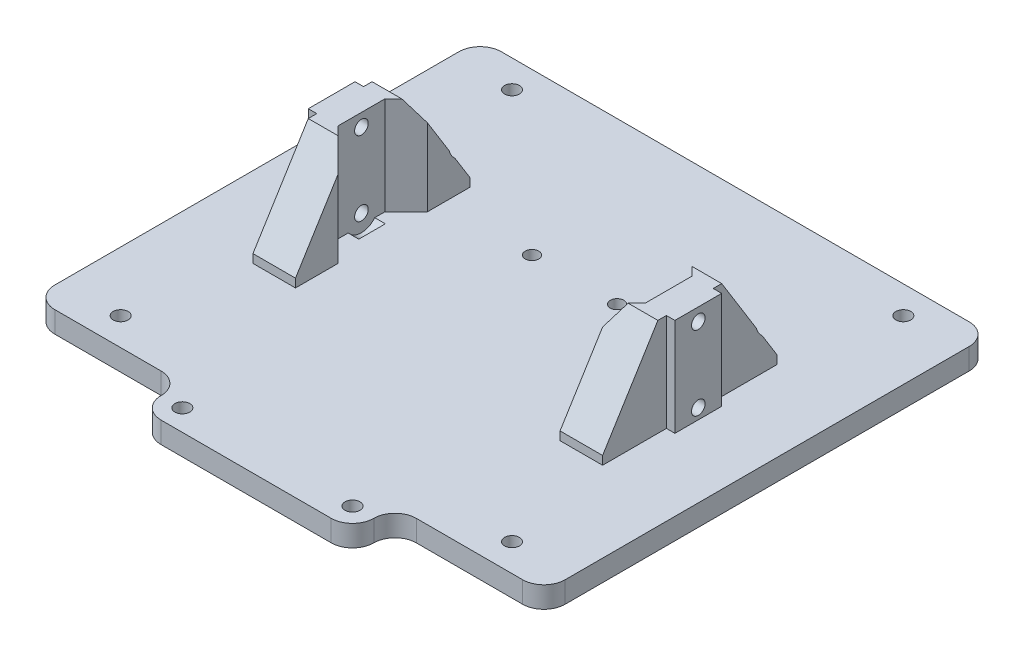
SolidWorks part; units mm, degrees
ref_plane "정면" through (0, 0, 0) normal (0, 0, 1) x (1, 0, 0)
ref_plane "윗면" through (0, 0, 0) normal (0, 1, 0) x (1, 0, 0)
ref_plane "우측면" through (0, 0, 0) normal (1, 0, 0) x (0, 0, -1)
sketch "스케치1" plane through (0, 0, 0) normal (0, 1, 0) x (1, 0, 0)
  line L0 (-25, -52.5) -> (-60, -52.5)
  line L1 (60, 52.5) -> (-60, 52.5)
  line L2 (60, 52.5) -> (60, -52.5)
  line L3 (60, -52.5) -> (25, -52.5)
  line L4 (-60, 52.5) -> (-60, -52.5)
  line L5 (60, 52.5) -> (-60, -52.5) construction
  line L6 (60, -52.5) -> (-60, 52.5) construction
  line L7 (25, -62.5) -> (-25, -62.5)
  line L8 (25, -62.5) -> (25, -52.5)
  line L10 (-25, -62.5) -> (-25, -52.5)
  line L11 (25, -62.5) -> (-25, -52.5) construction
  line L12 (25, -52.5) -> (-25, -62.5) construction
  point P0 (0, 0)
  point P6 (0, -57.5)
  dimension "D1" = 120
  dimension "D2" = 105
  dimension "D3" = 50
  dimension "D4" = 10
extrude "보스-돌출1" add sketch "스케치1" along normal blind 5
fillet "필렛1" radius 5 8 edges at (60, 2.5, -52.5) (60, 2.5, 52.5) (-60, 2.5, -52.5) (-60, 2.5, 52.5) (-25, 2.5, 52.5) (25, 2.5, 52.5) (25, 2.5, 62.5) (-25, 2.5, 62.5)
sketch "스케치2" plane through (0, 5, 0) normal (0, 1, 0) x (1, 0, 0)
  line L0 (-43.1, 29.5) -> (-43.1, -5.3) construction
  line L1 (-36.1, -4.8) -> (-43.1, -4.8)
  line L2 (-36.1, -4.8) -> (-36.1, 6.2)
  line L3 (-36.1, 6.2) -> (-43.1, 6.2)
  line L4 (-43.1, -4.8) -> (-43.1, 6.2)
  line L5 (-61.9, -0.8) -> (-43.1, -0.8) construction
  line L6 (-43.1, 2.2) -> (-61.9, 2.2) construction
  dimension "D1" = 7
  dimension "D2" = 4
  dimension "D3" = 4
extrude "보스-돌출2" add sketch "스케치2" along normal blind 23 separate body
sketch "스케치3" plane through (-36.1, 0, 0) normal (1, 0, 0) x (0, 0, -1)
  circle A0 centre (0.7, 7.5) radius 1.5 construction
  circle A1 centre (0.7, 25) radius 1.5 construction
  circle A2 centre (0.7, 25) radius 1.6
  circle A3 centre (0.7, 7.5) radius 1.6
  circle A4 centre (0.7, 7.5) radius 1.5 construction
  circle A5 centre (0.7, 25) radius 1.5 construction
  dimension "D1" = 3.2
  dimension "D2" = 3.2
extrude "컷-돌출1" cut sketch "스케치3" against normal through all
mirror "대칭 복사1" about plane through (0, 0, 0) normal (1, 0, 0) of bodies 103
sketch "스케치5" plane through (0, 5, 0) normal (0, 1, 0) x (1, 0, 0)
  circle A0 centre (-46, -46) radius 1.75 construction
  circle A1 centre (-46, 46) radius 1.75 construction
  circle A2 centre (46, 46) radius 1.75 construction
  circle A3 centre (46, -46) radius 1.75 construction
  circle A4 centre (-46, -46) radius 1.75
  circle A5 centre (-46, 46) radius 1.75
  circle A6 centre (46, 46) radius 1.75
  circle A7 centre (46, -46) radius 1.75
extrude "컷-돌출3" cut sketch "스케치5" against normal through all
sketch "스케치6" plane through (0, 5, 0) normal (0, 1, 0) x (1, 0, 0)
  circle A0 centre (20, -57.5) radius 1.75 construction
  circle A1 centre (-20, -57.5) radius 1.75 construction
  circle A2 centre (20, -57.5) radius 1.75
  circle A3 centre (-20, -57.5) radius 1.75
extrude "컷-돌출4" cut sketch "스케치6" against normal through all
sketch "Sketch2" plane through (36.1, 0, 0) normal (-1, 0, 0) x (0, 0, 1)
  circle A0 centre (-0.7, 7.5) radius 4
  dimension "D1" = 8
extrude "Cut-Extrude1" cut sketch "Sketch2" along normal blind 2.5
sketch "Sketch3" plane through (-36.1, 0, 0) normal (1, 0, 0) x (0, 0, -1)
  circle A0 centre (0.7, 7.5) radius 4
  dimension "D1" = 8
extrude "Cut-Extrude2" cut sketch "Sketch3" along normal blind 2.5
sketch "Sketch4" plane through (0, 5, 0) normal (0, 1, 0) x (1, 0, 0)
  line L0 (-10, 0) -> (10, 0) construction
  line L1 (10, 0) -> (10, 14.7) construction
  line L2 (10, 14.7) -> (-10, 14.7) construction
  line L3 (-10, 14.7) -> (-10, 0) construction
  line L4 (55, 52.5) -> (-55, 52.5) construction
  circle A0 centre (10, 0) radius 1.5 construction
  circle A1 centre (-10, 0) radius 1.5 construction
  circle A2 centre (10, 0) radius 1.5 construction
  circle A3 centre (-10, 0) radius 1.5 construction
  circle A4 centre (-10, 0) radius 1.6
  circle A5 centre (10, 0) radius 1.6
  circle A6 centre (-10, 14.7) radius 1.6
  circle A7 centre (10, 14.7) radius 1.6
  dimension "D1" = 3.2
  dimension "D2" = 3.2
  dimension "D3" = 37.8
extrude "Cut-Extrude3" cut sketch "Sketch4" against normal through all and the other way through all
sketch "스케치9" plane through (-36.1, 0, 0) normal (1, 0, 0) x (0, 0, -1)
  line L0 (-4.8, 5) -> (6.2, 5) construction
  line L1 (-4.8, 5) -> (-19.8, 5)
  line L2 (-4.8, 5) -> (-4.8, 28)
  line L3 (-4.8, 28) -> (-19.8, 28)
  line L4 (-19.8, 5) -> (-19.8, 28)
  line L5 (-4.8, 28) -> (-4.8, 5) construction
  line L6 (8.2, 28) -> (21.2, 7)
  line L7 (-19.8, 7) -> (-6.8, 28)
  line L8 (6.2, 5) -> (21.2, 5)
  line L9 (6.2, 5) -> (6.2, 28)
  line L10 (6.2, 28) -> (21.2, 28)
  line L11 (21.2, 5) -> (21.2, 28)
  line L12 (-4.8, 28) -> (6.2, 28) construction
  circle A1 centre (20.7, 16) radius 4.5
  circle A2 centre (0.7, 25) radius 1.6 construction
  line M13 (6.2, 5) -> (6.2, 28)
  line M15 (-4.8, 28) -> (-4.8, 5)
  dimension "D3" = 11
  dimension "D5" = 9
  dimension "D1" = 15
  dimension "D2" = 15
  dimension "D4" = 20
  dimension "D6" = 2
  dimension "D7" = 2
  dimension "D8" = 2
  dimension "D9" = 2
extrude "보스-돌출4" add sketch "스케치9" along normal blind 5 and the other way blind 5 contours L7 L4 L1 L3 M15 | A1 L6 L10 L8 L11 M13 region at (-36.1, 13.554, 10.2269) region at (-36.1, 13.5537, -11.6185)
sketch "스케치10" plane through (36.1, 0, 0) normal (-1, 0, 0) x (0, 0, 1)
  line L0 (4.8, 28) -> (-6.2, 28) construction
  line L1 (-6.2, 5) -> (-21.2, 5)
  line L2 (-6.2, 5) -> (-6.2, 28)
  line L3 (-6.2, 28) -> (-21.2, 28)
  line L4 (-21.2, 5) -> (-21.2, 28)
  line L5 (4.8, 28) -> (19.8, 28)
  line L6 (4.8, 28) -> (4.8, 5)
  line L7 (4.8, 5) -> (19.8, 5)
  line L8 (19.8, 28) -> (19.8, 5)
  line L9 (-8.2, 28) -> (-21.2, 7)
  line L10 (6.8, 28) -> (19.8, 7)
  line L11 (4.8, 5) -> (-6.2, 5) construction
  circle A0 centre (-20.7, 16) radius 4.5
  circle A1 centre (-0.7, 25) radius 1.6 construction
  line M13 (4.8, 5) -> (4.8, 28)
  line M15 (-6.2, 28) -> (-6.2, 5)
  dimension "D7" = 9
  dimension "D1" = 15
  dimension "D2" = 15
  dimension "D3" = 2
  dimension "D4" = 2
  dimension "D5" = 2
  dimension "D6" = 2
  dimension "D8" = 20
  dimension "D9" = 11
extrude "보스-돌출5" add sketch "스케치10" along normal blind 5 and the other way blind 5 contours A0 L9 L4 L1 L3 M15 | L10 L5 L7 L8 M13 region at (36.1, 13.5537, -11.6185) region at (36.1, 13.554, 10.2269)
chamfer "모따기1" distance 5 4 edges at (-31.1, 16.5, -6.2) (-31.1, 16.5, 4.8) (31.1, 16.5, -6.2) (31.1, 16.5, 4.8)
sketch "스케치12" plane through (0, 5, 0) normal (0, 1, 0) x (1, 0, 0)
  circle A0 centre (-10, 0) radius 1.6
  circle A1 centre (10, 0) radius 1.6
extrude "보스-돌출6" add sketch "스케치12" against normal blind 5
